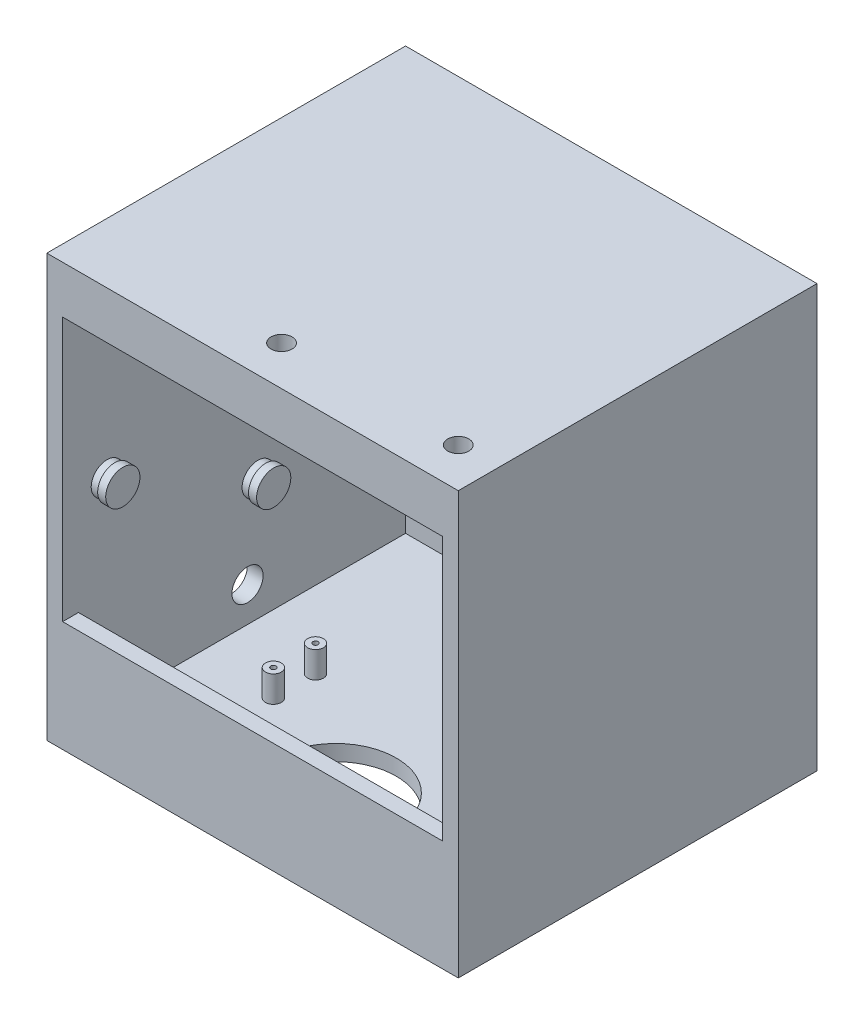
SolidWorks part; units mm, degrees
ref_plane "Front Plane" through (0, 0, 0) normal (0, 0, 1) x (1, 0, 0)
ref_plane "Top Plane" through (0, 0, 0) normal (0, 1, 0) x (1, 0, 0)
ref_plane "Right Plane" through (0, 0, 0) normal (1, 0, 0) x (0, 0, -1)
sketch "Base Plate Sketch" plane through (0, 0, 0) normal (0, 1, 0) x (1, 0, 0)
  line L1 (-176.9042, 232.645) -> (280.2958, 232.645)
  line L2 (-176.9042, 232.645) -> (-176.9042, -161.055)
  line L3 (-176.9042, -161.055) -> (280.2958, -161.055)
  line L4 (280.2958, 232.645) -> (280.2958, -161.055)
  line L5 (-195.9542, 251.695) -> (299.3458, 251.695)
  line L6 (-195.9542, 251.695) -> (-195.9542, -180.105)
  line L7 (-195.9542, -180.105) -> (299.3458, -180.105)
  line L8 (299.3458, 251.695) -> (299.3458, -180.105)
  line L9 (51.6958, 232.645) -> (51.6958, -161.055)
  circle A0 centre (51.6958, -80.0925) radius 73.025
  circle A1 centre (-72.1292, -82.0299) radius 4.1
  circle A2 centre (-72.1292, 203.67) radius 4.7625
  circle A3 centre (-84.8292, 32.22) radius 9.5
  circle A4 centre (-84.8292, -18.5299) radius 9.5
  circle A5 centre (-84.8292, 32.22) radius 3.175
  circle A6 centre (-84.8292, -18.5299) radius 3.175
  circle A7 centre (175.5208, -82.0299) radius 4.1
  circle A8 centre (188.2208, -18.5299) radius 3.175
  circle A9 centre (188.2208, -18.5299) radius 9.5
  circle A10 centre (188.2208, 32.22) radius 3.175
  circle A11 centre (188.2208, 32.22) radius 9.5
  circle A12 centre (175.5208, 203.67) radius 4.7625
  dimension "D7" = 146.05
  dimension "D9" = 8.2
  dimension "D10" = 12.7
  dimension "D11" = 63.5
  dimension "D12" = 9.525
  dimension "D13" = 12.7
  dimension "D14" = 19
  dimension "D15" = 19
  dimension "D19" = 6.35
  dimension "D20" = 6.35
  dimension "D1" = 393.7
  dimension "D2" = 457.2
  dimension "D3" = 19.05
  dimension "D4" = 19.05
  dimension "D5" = 19.05
  dimension "D6" = 19.05
  dimension "D8" = 312.7375
  dimension "D16" = 50.75
  dimension "D17" = 123.825
  dimension "D21" = 28.975
  dimension "D22" = 171.45
extrude "Boss-Extrude2" add sketch "Base Plate Sketch" along normal blind 31.75 contours A10 | A11 | A8 | A9 | A5 | A3 | A6 | A4
extrude "Boss-Extrude3" add sketch "Sketch1<5>" against normal blind 19.05 contours L5 L8 L7 L6
sketch "Sketch1<5>" plane through (0, 0, 0) normal (0, 1, 0) x (1, 0, 0) same geometry as "Base Plate Sketch"
extrude "Cut-Extrude1" cut sketch "Sketch1<6>" against normal blind 99.05 contours A2 | A1 | A0 | A7 | A12
sketch "Sketch1<6>" plane through (0, 0, 0) normal (0, 1, 0) x (1, 0, 0) same geometry as "Base Plate Sketch"
extrude "Boss-Extrude4" add sketch "Sketch1<7>" along normal blind 469.9 contours L6 L7 L8 L5 | L2 L3 L4 L1
sketch "Sketch1<7>" plane through (0, 0, 0) normal (0, 1, 0) x (1, 0, 0) same geometry as "Base Plate Sketch"
ref_plane "Plane1" through (-176.9042, 0, -232.645) normal (1, 0, 0) x (0, 0, -1)
sketch "Back Wall Sketch" plane through (0, 0, -232.645) normal (0, 0, 1) x (1, 0, 0)
  line L0 (-176.9042, 114.3) -> (280.2958, 114.3)
  line L1 (-176.9042, 469.9) -> (-176.9042, 0) construction
  line L2 (280.2958, 469.9) -> (280.2958, 0) construction
  line L3 (-176.9042, 266.7) -> (280.2958, 266.7)
  line L4 (-176.9042, 0) -> (280.2958, 0) construction
  line L5 (-176.9042, 469.9) -> (280.2958, 469.9) construction
  line L6 (51.6958, 266.7) -> (51.6958, 469.9)
  line L7 (280.2958, 266.7) -> (280.2958, 114.3)
  line L8 (-176.9042, 266.7) -> (-176.9042, 114.3)
  circle A0 centre (-117.9716, 342.325) radius 1.875
  circle A2 centre (-21.0417, 294.9875) radius 1.875
  circle A4 centre (-117.9716, 316.575) radius 1.875
  circle A5 centre (124.4333, 294.9875) radius 1.875
  circle A6 centre (221.3633, 342.325) radius 1.875
  circle A7 centre (221.3633, 316.575) radius 1.875
  circle A8 centre (184.1213, 148.3) radius 16.8
  dimension "D3" = 3.75
  dimension "D4" = 3.75
  dimension "D5" = 3.75
  dimension "D10" = 33.6
  dimension "D1" = 114.3
  dimension "D2" = 152.4
  dimension "D6" = 127.575
  dimension "D7" = 25.75
  dimension "D8" = 174.9125
  dimension "D9" = 155.8625
  dimension "D11" = 96.1746
  dimension "D12" = 118.4
extrude "Boss-Extrude5" add sketch "Back Wall Sketch" against normal blind 38.3 contours L8 L0 L7 L3
extrude "Cut-Extrude2" cut sketch "Back Wall Sketch<5>" against normal blind 19.25 contours L3 L7 L0 L8
sketch "Back Wall Sketch<5>" plane through (0, 0, -232.645) normal (0, 0, 1) x (1, 0, 0) same geometry as "Back Wall Sketch"
extrude "Cut-Extrude5" cut sketch "Back Wall Sketch<7>" against normal blind 28.875 contours A8
sketch "Back Wall Sketch<7>" plane through (0, 0, -232.645) normal (0, 0, 1) x (1, 0, 0) same geometry as "Back Wall Sketch"
extrude "Cut-Extrude6" cut sketch "Back Wall Sketch<8>" against normal blind 28.875 contours A2 | A4 | A0 | A6 | A7 | A5
sketch "Back Wall Sketch<8>" plane through (0, 0, -232.645) normal (0, 0, 1) x (1, 0, 0) same geometry as "Back Wall Sketch"
sketch "Left Wall Sketch" plane through (-176.9042, 0, 0) normal (1, 0, 0) x (0, 0, -1)
  line L0 (232.645, 0) -> (-161.055, 0) construction
  line L1 (251.695, 266.7) -> (251.695, 114.3) construction
  line L2 (232.645, 114.3) -> (232.645, 0) construction
  circle A0 centre (-126.7142, 237.44) radius 19
  circle A1 centre (54.8951, 146) radius 19
  circle A2 centre (42.445, 41.61) radius 18.75
  dimension "D1" = 38
  dimension "D2" = 38
  dimension "D3" = 37.5
  dimension "D5" = 146
  dimension "D9" = 41.61
  dimension "D4" = 237.44
  dimension "D6" = 378.4092
  dimension "D7" = 196.8
  dimension "D8" = 190.2
extrude "Cut-Extrude7" cut sketch "Left Wall Sketch" against normal blind 28.875 contours A2
extrude "Boss-Extrude6" add sketch "Left Wall Sketch<3>" along normal blind 9.35 contours A1 | A0
sketch "Left Wall Sketch<3>" plane through (-176.9042, 0, 0) normal (1, 0, 0) x (0, 0, -1) same geometry as "Left Wall Sketch"
sketch "Sketch5" plane through (-167.5542, 0, 0) normal (1, 0, 0) x (0, 0, -1)
  circle A0 centre (-126.7142, 237.44) radius 20.6
  circle A1 centre (54.8951, 146) radius 20.6
  dimension "D1" = 41.2
  dimension "D2" = 41.2
extrude "Boss-Extrude7" add sketch "Sketch5" along normal blind 9.7
sketch "Chamber Door Sketch" plane through (0, 0, 161.055) normal (0, 0, -1) x (-1, 0, 0)
  line L0 (-280.2958, 431.8) -> (176.9042, 431.8)
  line L1 (-280.2958, 469.9) -> (-280.2958, 0) construction
  line L2 (176.9042, 469.9) -> (176.9042, 0) construction
  line L3 (-280.2958, 114.3) -> (176.9042, 114.3)
  line L4 (176.9042, 0) -> (-280.2958, 0) construction
  line L5 (176.9042, 469.9) -> (-280.2958, 469.9) construction
  line L6 (-280.2958, 431.8) -> (-280.2958, 114.3)
  line L7 (176.9042, 431.8) -> (176.9042, 114.3)
  dimension "D1" = 114.3
  dimension "D2" = 38.1
extrude "Cut-Extrude8" cut sketch "Chamber Door Sketch" against normal blind 25.4 contours L0 L7 L3 L6
sketch "Top Sketch" plane through (0, 469.9, 0) normal (0, 1, 0) x (1, 0, 0)
  line L1 (-195.9542, 251.695) -> (299.3458, 251.695)
  line L2 (-195.9542, 251.695) -> (-195.9542, -180.105)
  line L3 (-195.9542, -180.105) -> (299.3458, -180.105)
  line L4 (299.3458, 251.695) -> (299.3458, -180.105)
extrude "Boss-Extrude8" add sketch "Top Sketch" along normal blind 19.05 contours L4 L3 L2 L1
sketch "Sketch7" plane through (0, 469.9, 0) normal (0, -1, 0) x (1, 0, 0)
  line L0 (-176.9042, -232.645) -> (280.2958, -232.645) construction
  line L1 (22.0201, -181.825) -> (11.0101, -162.755)
  line L2 (11.0101, -162.755) -> (-11.0101, -162.755)
  line L3 (-11.0101, -162.755) -> (-22.0201, -181.825)
  line L4 (-22.0201, -181.825) -> (-11.0101, -200.895)
  line L5 (-11.0101, -200.895) -> (11.0101, -200.895)
  line L6 (11.0101, -200.895) -> (22.0201, -181.825)
  circle A0 centre (0, -181.825) radius 19.07 construction
  point P1 (0, -200.895)
  dimension "D1" = 38.14
  dimension "D2" = 31.75
extrude "Boss-Extrude9" add sketch "Sketch7" along normal blind 12.7 contours L2 L3 L4 L5 L6 L1
sketch "Sketch8" plane through (0, 488.95, 0) normal (0, 1, 0) x (1, 0, 0)
  line L2 (-195.9542, -180.105) -> (299.3458, -180.105) construction
  line L3 (-195.9542, 251.695) -> (-195.9542, -180.105) construction
  line L4 (299.3458, 251.695) -> (299.3458, -180.105) construction
  circle A0 centre (38.9958, -132.48) radius 12.7
  circle A1 centre (251.7208, -132.48) radius 12.7
  point P4 (0, 0)
  dimension "D1" = 47.625
  dimension "D4" = 25.4
  dimension "D2" = 234.95
  dimension "D3" = 47.625
extrude "Cut-Extrude9" cut sketch "Sketch8" against normal up to next (19.05 mm away)
